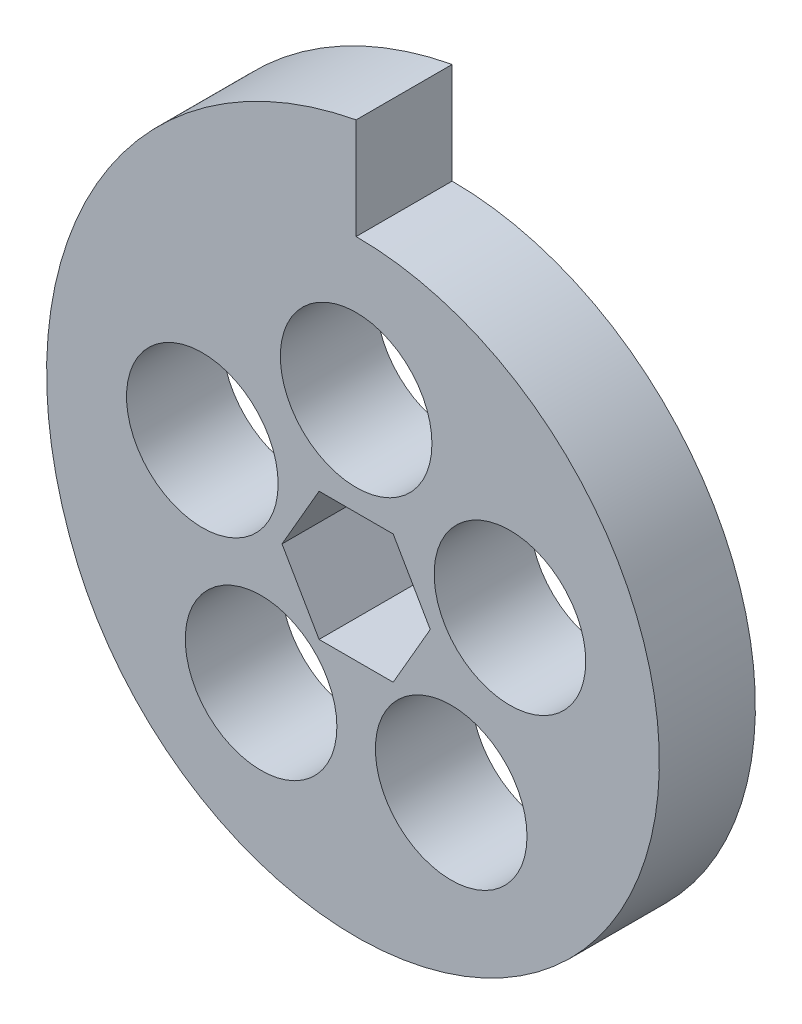
SolidWorks part; units mm, degrees
material "AISI 1020"
ref_plane "Front Plane" through (0, 0, 0) normal (0, 0, 1) x (1, 0, 0)
ref_plane "Top Plane" through (0, 0, 0) normal (0, 1, 0) x (1, 0, 0)
ref_plane "Right Plane" through (0, 0, 0) normal (1, 0, 0) x (0, 0, -1)
sketch "Sketch3" plane through (0, 0, 0) normal (0, 0, 1) x (1, 0, 0)
  line L5 (0, 30) -> (0, 40)
  line L6 (7.3323, 0) -> (3.6662, 6.35)
  line L7 (3.6662, 6.35) -> (-3.6662, 6.35)
  line L8 (-3.6662, 6.35) -> (-7.3323, 0)
  line L9 (-7.3323, 0) -> (-3.6662, -6.35)
  line L10 (-3.6662, -6.35) -> (3.6662, -6.35)
  line L11 (3.6662, -6.35) -> (7.3323, 0)
  circle A2 centre (0, 0) radius 30 construction
  circle A3 centre (0, 0) radius 6.35 construction
  circle A4 centre (0, 16) radius 7.5
  circle A5 centre (15.2169, 4.9443) radius 7.5
  circle A6 centre (9.4046, -12.9443) radius 7.5
  circle A7 centre (-9.4046, -12.9443) radius 7.5
  circle A8 centre (-15.2169, 4.9443) radius 7.5
  arc A9 (0, 40) -> (-27.5501, -11.874) centre (7.013, 3.0226) ccw
  arc A10 (0, 30) -> (-27.5501, -11.874) centre (0, 0) cw
  point P3 (0, 0)
  point P25 (0, 0)
  dimension "D2" = 10
  dimension "D1" = 60
  dimension "D4" = 15
  dimension "D3" = 12.7
  dimension "D5" = 16
  dimension "D6" = 5
extrude "Boss-Extrude1" add sketch "Sketch3" along normal blind 9.5
